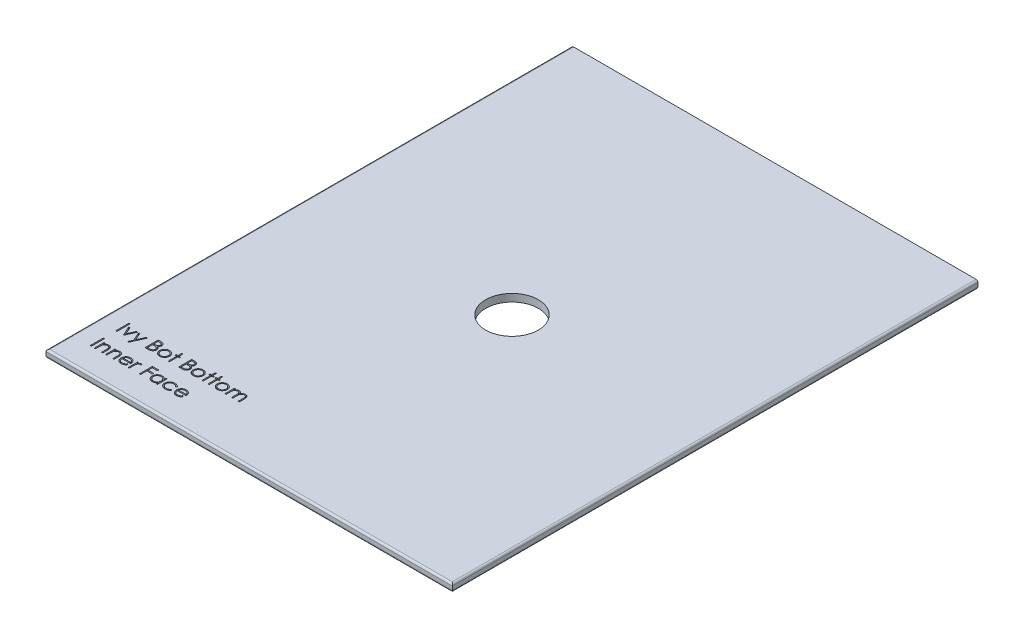
SolidWorks part; units mm, degrees
ref_plane "Front Plane" through (0, 0, 0) normal (0, 0, 1) x (1, 0, 0)
ref_plane "Top Plane" through (0, 0, 0) normal (0, 1, 0) x (1, 0, 0)
ref_plane "Right Plane" through (0, 0, 0) normal (1, 0, 0) x (0, 0, -1)
sketch "Sketch1" plane through (0, 0, 0) normal (0, 1, 0) x (1, 0, 0)
  line L1 (-54, 69.875) -> (54, 69.875)
  line L2 (-54, 69.875) -> (-54, -69.875)
  line L3 (-54, -69.875) -> (54, -69.875)
  line L4 (54, 69.875) -> (54, -69.875)
  point P4 (0, -69.875)
  point P6 (-54, 0)
  dimension "D1" = 108
  dimension "D2" = 139.75
extrude "Boss-Extrude1" add sketch "Sketch1" along normal blind 2 contours L1 L4 L3 L2
sketch "Sketch6" plane through (0, 2, 0) normal (0, 1, 0) x (1, 0, 0)
  circle A0 centre (0, 0) radius 7
  dimension "D1" = 14
extrude "Cut-Extrude1" cut sketch "Sketch6" against normal through all contours A0
fillet "Fillet1" radius 0.5 7 edges at (-54, 0, 0) (0, 0, -69.875) (0, 0, 69.875) (54, 0, 0) (54, 2, 0) (-54, 2, 0) (0, 2, 69.875)
sketch "Sketch9" plane through (0, 2, 0) normal (0, 1, 0) x (1, 0, 0)
  text T0 "Ivy Bot Bottom\r\nInner Face"
extrude "Cut-Extrude4" cut sketch "Sketch9" against normal blind 1
sketch "Sketch10" plane through (0, 0, 0) normal (0, -1, 0) x (1, 0, 0)
  line L0 (-12.9733, 25) -> (12.9733, 25) construction
  line L1 (-12.9733, -25) -> (12.9733, -25) construction
  text T0 "3               1"
  text T1 " 2               4"
  point P8 (0, 25)
  point P12 (0, -25)
  dimension "D1" = 25
  dimension "D2" = 25
extrude "Cut-Extrude5" cut sketch "Sketch10" against normal blind 1
